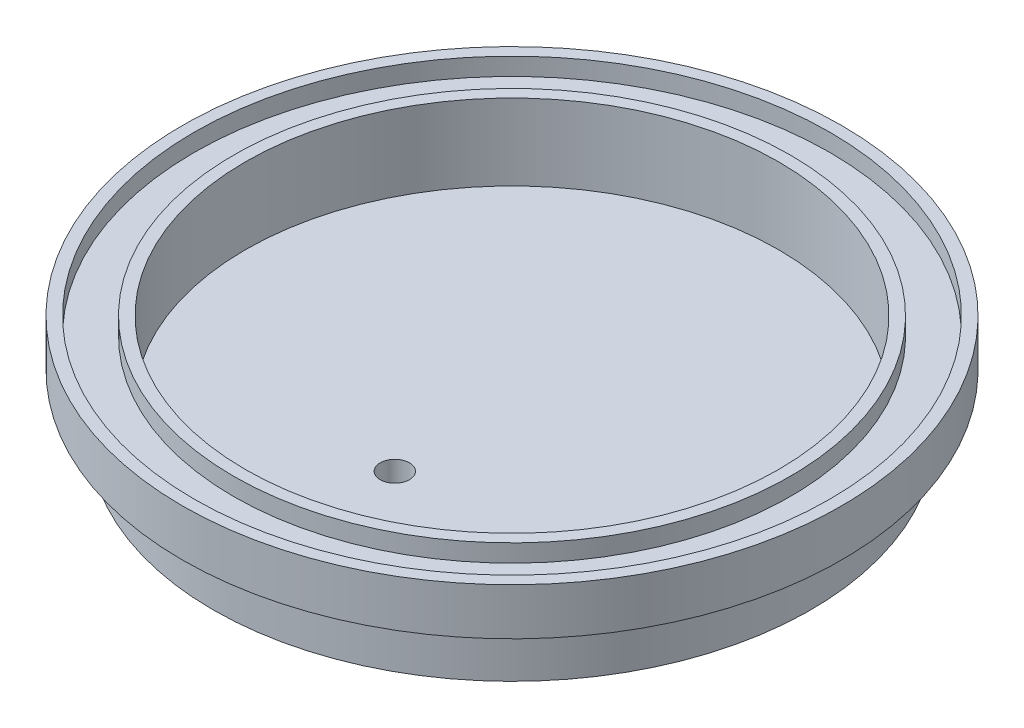
SolidWorks part; units mm, degrees
ref_plane "Front Plane" through (0, 0, 0) normal (0, 0, 1) x (1, 0, 0)
ref_plane "Top Plane" through (0, 0, 0) normal (0, 1, 0) x (1, 0, 0)
ref_plane "Right Plane" through (0, 0, 0) normal (1, 0, 0) x (0, 0, -1)
sketch "Sketch1" plane through (0, 0, 0) normal (0, 1, 0) x (1, 0, 0)
  circle A0 centre (0, 0) radius 51
  circle A1 centre (0, 0) radius 54.25
  circle A2 centre (0, 0) radius 56.25
  circle A3 centre (0, 0) radius 47.5
  circle A4 centre (0, 0) radius 45.5
  dimension "D1" = 102
  dimension "D3" = 108.5
  dimension "D5" = 95
  dimension "D2" = 2
  dimension "D4" = 2
extrude "Boss-Extrude1" add sketch "Sketch1" along normal blind 3 contours A2 A1 | A3 A4 region at (-54.659, 0, 0) region at (-46.1565, 0, 0)
extrude "Boss-Extrude2" add sketch "Sketch1<3>" against normal blind 15 separate body contours A0 | A4 | A3 A4 region at (-49.5575, 0, 0) region at (-46.1565, 0, 0) region at (0, 0, 0)
sketch "Sketch1<3>" plane through (0, 0, 0) normal (0, 1, 0) x (1, 0, 0) same geometry as "Sketch1"
extrude "Boss-Extrude3" add sketch "Sketch1<4>" against normal blind 5 contours A2
sketch "Sketch1<4>" plane through (0, 0, 0) normal (0, 1, 0) x (1, 0, 0) same geometry as "Sketch1"
sketch "Sketch2" plane through (0, -5, 0) normal (0, -1, 0) x (1, 0, 0)
  line L0 (0, 0) -> (0, -69.0566) construction
  line L1 (-2.35, -51) -> (2.35, -51) construction
  line L2 (-2.35, -51) -> (-2.35, -56)
  line L3 (-2.35, -56) -> (2.35, -56)
  line L4 (2.35, -51) -> (2.35, -56)
  line L5 (-2.35, -51) -> (2.35, -56) construction
  line L6 (-2.35, -56) -> (2.35, -51) construction
  line L8 (-2.35, -51) -> (2.35, -51) construction
  line L9 (-2.35, -51) -> (-2.35, -50)
  line L10 (-2.35, -50) -> (2.35, -50)
  line L11 (2.35, -51) -> (2.35, -50)
  line L12 (-2.35, -51) -> (2.35, -50) construction
  line L13 (-2.35, -50) -> (2.35, -51) construction
  circle A1 centre (0, 0) radius 51 construction
  point P4 (0, -53.5)
  point P9 (0, -51)
  point P16 (0, -50.5)
  dimension "D1" = 4.7
  dimension "D2" = 5
  dimension "D3" = 1
extrude "Boss-Extrude4" add sketch "Sketch2" along normal blind 5
extrude "Cut-Extrude1" cut sketch "Sketch1<5>" against normal blind 10 contours A4 region at (0, 0, 0)
sketch "Sketch1<5>" plane through (0, 0, 0) normal (0, 1, 0) x (1, 0, 0) same geometry as "Sketch1"
sketch "Sketch3" plane through (0, -10, 0) normal (0, 1, 0) x (1, 0, 0)
  line L0 (0, 56.3953) -> (0, -46.3953) construction
  line L1 (0, 0) -> (-79.8754, 0) construction
  circle A0 centre (0, -20) radius 2.5
  dimension "D1" = 5
  dimension "D2" = 20
extrude "Cut-Extrude2" cut sketch "Sketch3" against normal through all
